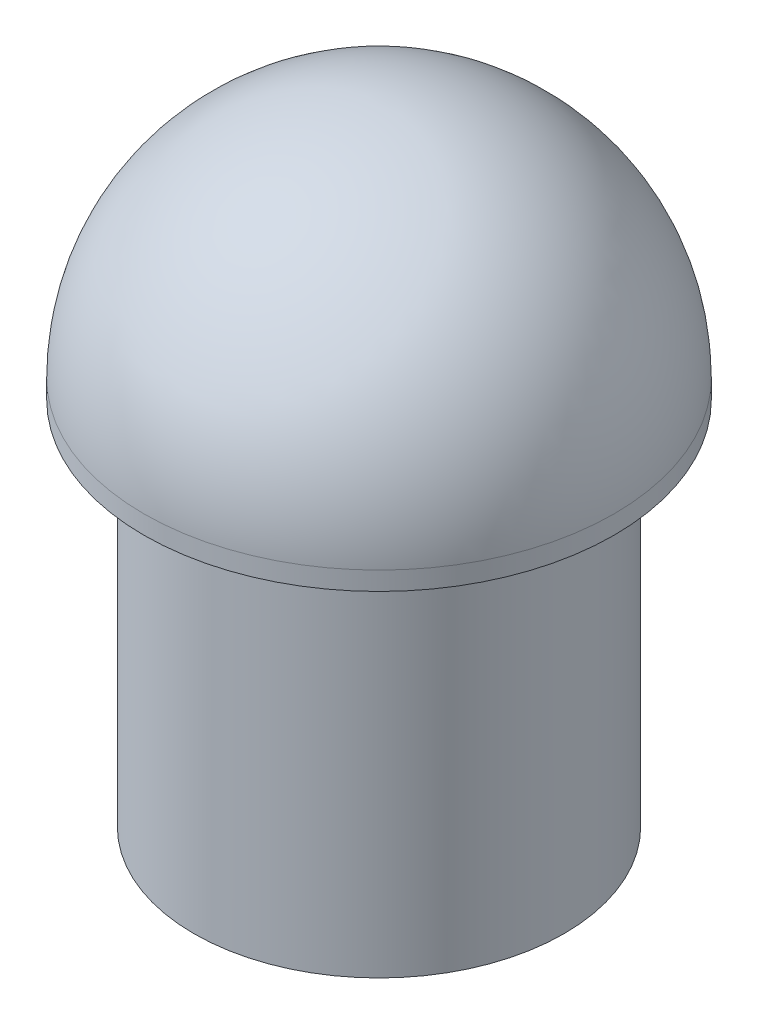
SolidWorks part; units mm, degrees
ref_plane "Front Plane" through (0, 0, 0) normal (0, 0, 1) x (1, 0, 0)
ref_plane "Top Plane" through (0, 0, 0) normal (0, 1, 0) x (1, 0, 0)
ref_plane "Right Plane" through (0, 0, 0) normal (1, 0, 0) x (0, 0, -1)
sketch "Sketch1" plane through (0, 0, 0) normal (0, 1, 0) x (1, 0, 0)
  circle A0 centre (0, 0) radius 6.35
extrude "Boss-Extrude1" add sketch "Sketch1" along normal blind 0.5
dome "Dome1" faces to dome 1 distance 6.35 reverse direction no elliptical dome no face at (0, 0.5, 6.35) parameters "D1"=6.35
sketch "Sketch2" plane through (0, 0, 0) normal (0, -1, 0) x (1, 0, 0)
  circle A0 centre (0, 0) radius 5
  circle A1 centre (0, 0) radius 3.3521
extrude "Boss-Extrude2" add sketch "Sketch2" along normal blind 10
